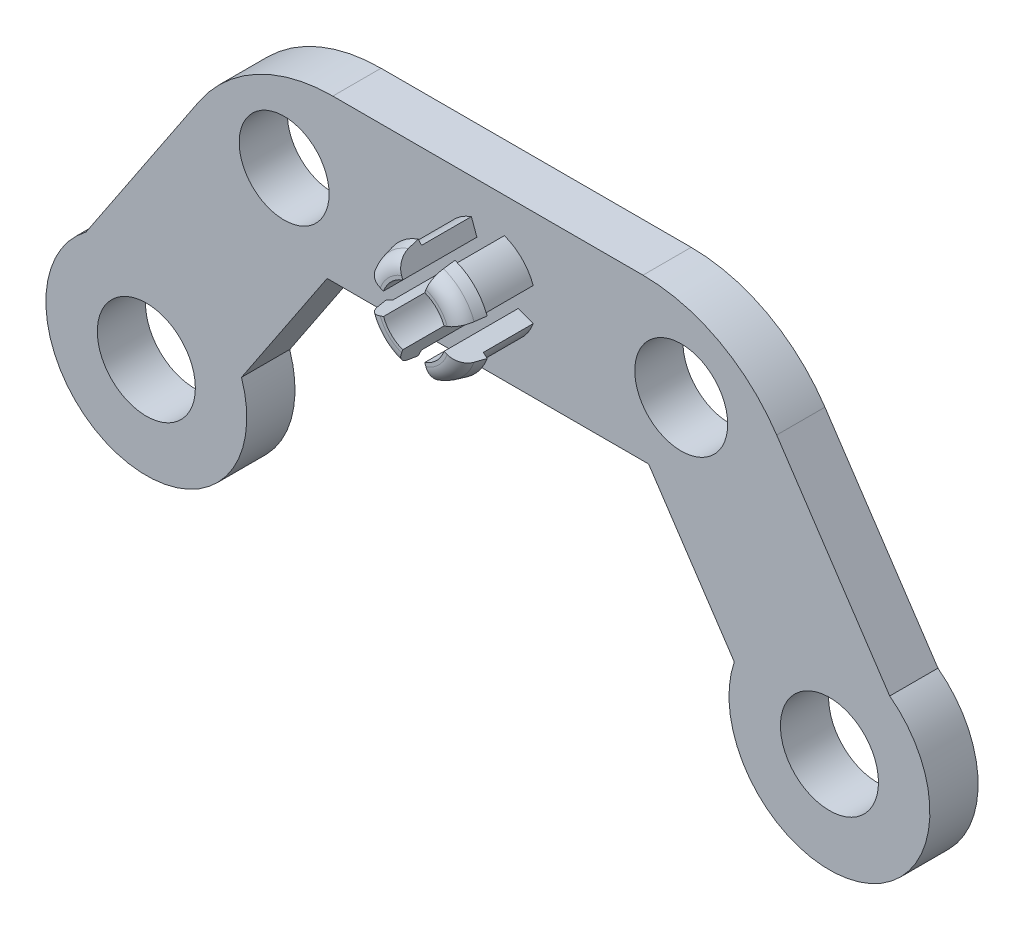
SolidWorks part; units mm, degrees
ref_plane "Płaszczyzna przednia" through (0, 0, 0) normal (0, 0, 1) x (1, 0, 0)
ref_plane "Płaszczyzna górna" through (0, 0, 0) normal (0, 1, 0) x (1, 0, 0)
ref_plane "Płaszczyzna prawa" through (0, 0, 0) normal (1, 0, 0) x (0, 0, -1)
sketch "Szkic1" plane through (0, 0, 0) normal (0, 0, 1) x (1, 0, 0)
  line L0 (-15, 0) -> (15, 0)
  line L1 (-10, -10) -> (10, -10)
  line L2 (-15, 0) -> (-25, -15)
  line L3 (-10, -10) -> (-15.3302, -17.9953)
  line L4 (10, -10) -> (15.3302, -17.9953)
  line L5 (15, 0) -> (25, -15)
  arc A0 (-25, -15) -> (-15.3302, -17.9953) centre (-21.25, -20) ccw
  arc A1 (15.3302, -17.9953) -> (25, -15) centre (21.25, -20) ccw
  circle A4 centre (21.25, -20) radius 3.05
  circle A5 centre (-21.25, -20) radius 3.05
  point P2 (0, 0)
  point P3 (0, -10)
  dimension "D6" = 6.25
  dimension "D7" = 6.1
  dimension "D8" = 6.1
  dimension "D1" = 30
  dimension "D2" = 10
  dimension "D3" = 20
  dimension "D4" = 15
  dimension "D5" = 50
  dimension "D9" = 5
extrude "Dodanie-wyciągnięcie1" add sketch "Szkic1" along normal blind 3
sketch "Szkic2" plane through (0, 0, 3) normal (0, 0, 1) x (1, 0, 0)
  circle A0 centre (-12.6768, -5.3987) radius 2.7974
  circle A1 centre (12.029, -5.3987) radius 2.8908
extrude "Wytnij-wyciągnięcie1" cut sketch "Szkic2" against normal blind 10
fillet "Zaokrąglenie1" radius 10 2 edges at (-15, 0, 1.5) (15, 0, 1.5)
sketch "Szkic3" plane through (0, 0, 3) normal (0, 0, 1) x (1, 0, 0)
  line L0 (-10, -10) -> (0, 0) construction
  line L1 (0, 0) -> (10, -10) construction
  line L2 (0, 0) -> (0, -10) construction
  line L3 (-10, -10) -> (10, -10) construction
  circle A0 centre (0, -5) radius 3
  dimension "D1" = 6
sketch "Szkic4" plane through (0, 0, 0) normal (1, 0, 0) x (0, 0, -1)
  line L0 (-3, -2) -> (-6.1, -2)
  line L1 (-3, 0) -> (-3, -10) construction
  line L2 (-6.1, -2) -> (-6.1935, -1.651)
  line L3 (-6.1935, -1.651) -> (-7.6115, -2)
  line L4 (-7.6115, -2) -> (-7.6115, -3)
  line L5 (-7.6115, -3) -> (-3, -3)
  line L6 (-3, -3) -> (-3, -2)
  dimension "D1" = 3.1
  dimension "D2" = 1.4603
  dimension "D3" = 0.3613
  dimension "D4" = 1
  dimension "D5" = 3
  dimension "D6" = 75
  dimension "D7" = 1
  dimension "D8" = 4.6115
sketch3d "Szkic 3D1"
  line L0 (0, -5, 3) -> (0, -5, 14.3037) construction
ref_point "Punkt1"
revolve "Obrót1" add sketch "Szkic4" angle 360 about L0
sketch "Szkic5" plane through (0, 0, 7.6115) normal (0, 0, 1) x (1, 0, 0)
  line L0 (0, -5) -> (-1.7101, -0.3015)
  line L1 (-1.7101, -0.3015) -> (1.7101, -0.3015)
  line L2 (1.7101, -0.3015) -> (0, -5)
  line L3 (0, 0) -> (0, -10) construction
  line L4 (4.6985, -6.7101) -> (0, -5)
  line L5 (4.6985, -3.2899) -> (4.6985, -6.7101)
  line L6 (0, -5) -> (4.6985, -3.2899)
  line L7 (-1.7101, -9.6985) -> (0, -5)
  line L8 (1.7101, -9.6985) -> (-1.7101, -9.6985)
  line L9 (0, -5) -> (1.7101, -9.6985)
  line L10 (-4.6985, -3.2899) -> (0, -5)
  line L11 (-4.6985, -6.7101) -> (-4.6985, -3.2899)
  line L12 (0, -5) -> (-4.6985, -6.7101)
  point P15 (0, -5)
  circle M3 centre (0, -5) radius 2
  circle M4 centre (0, -5) radius 3
  dimension "D1" = 5
  dimension "D2" = 5
  dimension "D3" = 20
  dimension "D4" = 4
extrude "Wytnij-wyciągnięcie3" cut sketch "Szkic5" against normal up to surface (4.6115 mm away) contours L2 L1 L0 M4 | L6 L4 M3 M4 | L2 L0 M4 M3 | L12 L10 M3 M4 | L9 L7 M3 M4 | L9 L7 L8 M4 | L6 L4 L5 M4 | L12 L10 L11 M4 region at (0, -2.5178, 7.6115) region at (2.4822, -5, 7.6115) region at (0, -7.4822, 7.6115) region at (-2.4822, -5, 7.6115) region at (0, -1.1148, 7.6115) region at (3.8852, -5, 7.6115) region at (0, -8.8852, 7.6115) region at (-3.8852, -5, 7.6115) up to face at (-18.2, -20, 3)
fillet "Zaokrąglenie2" radius 1 4 edges at (2.1213, -7.1213, 7.6115) (-2.1213, -7.1213, 7.6115) (-2.1213, -2.8787, 7.6115) (2.1213, -2.8787, 7.6115)
